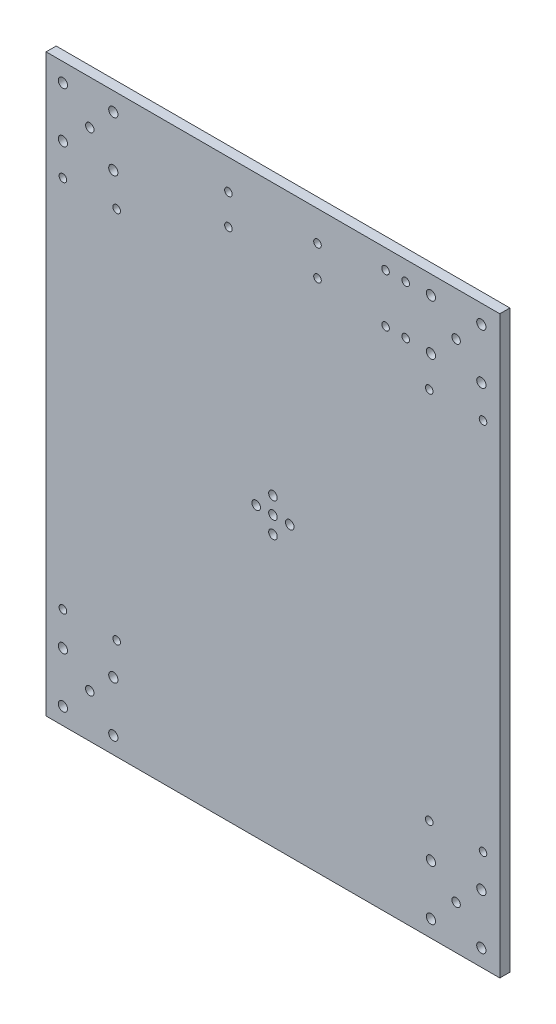
SolidWorks part; units mm, degrees
ref_plane "Спереди" through (0, 0, 0) normal (0, 0, 1) x (1, 0, 0)
ref_plane "Сверху" through (0, 0, 0) normal (0, 1, 0) x (1, 0, 0)
ref_plane "Справа" through (0, 0, 0) normal (1, 0, 0) x (0, 0, -1)
sketch "Эскиз3" plane through (0, 0, 0) normal (0, 0, 1) x (1, 0, 0)
  line L0 (0, 0) -> (0, 10) construction
  line L5 (135, -171.15) -> (-135, -171.15)
  line L6 (135, -171.15) -> (135, 171.15)
  line L7 (135, 171.15) -> (-135, 171.15)
  line L8 (-135, -171.15) -> (-135, 171.15)
  line L9 (0, 0) -> (10, 0) construction
  line L10 (0, 0) -> (0, -10) construction
  line L11 (0, 0) -> (-10, 0) construction
  line L12 (79, 130.65) -> (79, 159.65) construction
  line L13 (79, 159.65) -> (67, 159.65) construction
  line L14 (67, 159.65) -> (67, 130.65) construction
  line L15 (67, 130.65) -> (79, 130.65) construction
  circle A0 centre (0, 0) radius 2.55
  circle A1 centre (0, 10) radius 2.55
  circle A2 centre (10, 0) radius 2.55
  circle A3 centre (0, -10) radius 2.55
  circle A4 centre (-10, 0) radius 2.55
  circle A17 centre (67, 159.65) radius 2.25
  circle A18 centre (79, 159.65) radius 2.25
  circle A19 centre (67, 130.65) radius 2.25
  circle A20 centre (79, 130.65) radius 2.25
  point P0 (0, 0)
  point P5 (-135, 0)
  point P6 (0, 171.15)
  point P21 (0, 0)
  dimension "D3" = 5.1
  dimension "D4" = 5.1
  dimension "D7" = 4.5
  dimension "D1" = 342.3
  dimension "D2" = 270
  dimension "D5" = 10
  dimension "D6" = 4
extrude "Бобышка-Вытянуть1" add sketch "Эскиз3" along normal blind 6
sketch "Эскиз4" plane through (0, 0, 6) normal (0, 0, 1) x (1, 0, 0)
  line L0 (135, 171.15) -> (-135, 171.15) construction
  line L1 (-135, 171.15) -> (-135, -171.15) construction
  circle A0 centre (-109, 145.15) radius 2.5
  dimension "D1" = 5
  dimension "D2" = 26
  dimension "D3" = 26
extrude "Вырез-Вытянуть1" cut sketch "Эскиз4" against normal through all contours A0
pattern_linear "Линейный массив1" count 2 spacing 218 along (1, 0, 0) count 2 spacing 290.3 along (0, -1, 0) of "Вырез-Вытянуть1"
sketch "Эскиз7" plane through (0, 0, 0) normal (0, 0, -1) x (-1, 0, 0)
  line L9 (-26.5, 153.15) -> (26.5, 153.15) construction
  line L10 (-26.5, 153.15) -> (-26.5, 135.15) construction
  line L11 (-26.5, 135.15) -> (26.5, 135.15) construction
  line L16 (26.5, 153.15) -> (26.5, 135.15) construction
  line L17 (-135, 171.15) -> (135, 171.15) construction
  circle A0 centre (-26.5, 153.15) radius 2.25
  circle A1 centre (26.5, 153.15) radius 2.25
  circle A2 centre (-26.5, 135.15) radius 2.25
  circle A3 centre (26.5, 135.15) radius 2.25
  point P4 (0, 135.15)
  dimension "D4" = 4.5
  dimension "D5" = 4.5
  dimension "D6" = 4.5
  dimension "D7" = 4.5
  dimension "D1" = 53
  dimension "D2" = 18
  dimension "D3" = 18
extrude "Вырез-Вытянуть2" cut sketch "Эскиз7" against normal through all
sketch "Эскиз8" plane through (0, 0, 0) normal (0, 0, -1) x (-1, 0, 0)
  line L0 (93, 111.15) -> (125, 111.15) construction
  line L8 (135, 171.15) -> (135, -171.15) construction
  line L9 (-135, 171.15) -> (135, 171.15) construction
  circle A4 centre (93, 111.15) radius 2.25
  circle A5 centre (125, 111.15) radius 2.25
  dimension "D3" = 32
  dimension "D4" = 10
  dimension "D5" = 60
  dimension "D1" = 4.5
  dimension "D2" = 4.5
extrude "Вырез-Вытянуть3" cut sketch "Эскиз8" against normal through all
pattern_linear "Линейный массив2" count 2 spacing 222.3 along (0, -1, 0) count 2 spacing 218 along (1, 0, 0) of "Вырез-Вытянуть3"
sketch "Эскиз10" plane through (0, 0, 0) normal (0, 0, -1) x (-1, 0, 0)
  line L0 (-124, 130.15) -> (-94, 130.15) construction
  line L1 (-129, 125.15) -> (-89, 125.15) construction
  line L2 (-129, 125.15) -> (-129, 165.15) construction
  line L3 (-129, 165.15) -> (-89, 165.15) construction
  line L4 (-89, 125.15) -> (-89, 165.15) construction
  line L5 (-129, 125.15) -> (-89, 165.15) construction
  line L6 (-129, 165.15) -> (-89, 125.15) construction
  line L8 (-94, 130.15) -> (-94, 160.15) construction
  line L10 (-94, 160.15) -> (-124, 160.15) construction
  circle A0 centre (-124, 160.15) radius 2.75
  circle A1 centre (-94, 160.15) radius 2.75
  circle A2 centre (-94, 130.15) radius 2.75
  circle A3 centre (-124, 130.15) radius 2.75
  point P0 (-109, 145.15)
  dimension "D2" = 5.5
  dimension "D1" = 40
  dimension "D3" = 30
extrude "Вырез-Вытянуть4" cut sketch "Эскиз10" against normal through all
pattern_linear "Линейный массив3" count 2 spacing 219 along (-1, 0, 0) count 2 spacing 291.3 along (0, -1, 0) of "Вырез-Вытянуть4"
equation "\"Ширина груза\"= 160"
equation "\"Глубина груза\"= 240"
equation "\"Высота груза\"= 160"
equation "\"Ширина ячейки\"= \"Ширина груза\" + 10"
equation "\"Глубина ячейки\"= \"Глубина груза\" + 10"
equation "\"Высота ячейки\"= \"Высота груза\" + 10 + 13"
equation "\"Колво ячеек ширина\"= 2"
equation "\"Колво ячеек высота\"= 2"
equation "\"Толщина стенки\" = \"Толщина тонких панелей\""
equation "\"Крепление дверцы\"= 5 "
equation "\"Ширина рейки\"= \"Толщина шестерни\""
equation "\"Высота рейки\"= 20"
equation "\"Высота пола\" = 2*\"Толщина тонких панелей\""
equation "\"Колво полозьев\"= 5"
equation "\"Отступ рейки\"= 20"
equation "\"Глубина каретки\"= \"Глубина ячейки\" + 30 + \"Мотор Y высота корпуса\" + 20"
equation "\"Длинна рейки\" = (\"Ширина ячейки\"+\"Толщина вертикальных стенок\"+\"Крепление дверцы\")*\"Колво ячеек ширина\"+\"Ширина ячейки выгрузки\"*\"Колво выгрузки\"+\"Толщина вертикальных стенок\"+2*\"Отступ крепления мотора фиксации\"-\"Крепление дверцы\"*\"Колво ячеек ширина\""
equation "\"Отступ шпильки\"= 26"
equation "\"Диаметр шпильки\"= 5"
equation "\"D1@Бобышка-Вытянуть1\" = \"Толщина стенки\""
equation "\"D1@Эскиз4\"= \"Диаметр шпильки\""
equation "\"D2@Эскиз4\"=\"Отступ шпильки\""
equation "\"D3@Эскиз4\"= \"Отступ шпильки\""
equation "\"D2@Эскиз3\"=\"Ширина ячейки\" + \"Ширина пластины\" * 2"
equation "\"D1@Эскиз3\"=\"Глубина каретки\" "
equation "\"D3@Линейный массив1\"=\"Ширина ячейки\"  +\"Ширина пластины\" *2 - \"Отступ шпильки\" * 2"
equation "\"D4@Линейный массив1\"=\"Глубина каретки\" + \"Ширина рейки\" * 2 - \"Отступ шпильки\" * 2 - \"Ширина рейки\" * 2"
equation "\"Длинна шпильки\" = (\"Высота ячейки\"+\"Толщина горизонтальных плит\"+\"Высота пола\")*\"Колво ячеек высота\"+2*(\"Толщина горизонтальных плит\"+\"Отступ рейки\")"
equation "\"Ширина пластины\"= 50  "
equation "\"Высота зона выгрузки\"= \"Высота ячейки\" * 2 + \"Толщина стенки\" * 2"
equation "\"Колво выгрузки\"= 1"
equation "\"Отступ крепления мотора фиксации\" = (\"Ширина пластины\"+20-\"Толщина вертикальных стенок\")/2"
equation "\"Мотор X ширина корпуса\"= 42.3"
equation "\"Мотор X высота корпуса\"= 42.3"
equation "\"Мотор X длина корпуса\"= 40"
equation "\"Мотор X вылет вала\"= 19.8"
equation "\"Мотор Y ширина корпуса\"= 42.3"
equation "\"Мотор Y высота корпуса\"= 42.3"
equation "\"Мотор Y длина корпуса\"= 48"
equation "\"Мотор Y вылет вала\"= 30"
equation "\"Мотор Z ширина корпуса\"= 42"
equation "\"Мотор Z высота корпуса\"= 42"
equation "\"Мотор Z длина корпуса\"= 40"
equation "\"Мотор Z вылет вала\"= 23"
equation "\"Мотор диаметр вала ПРЕДВ\"= 5"
equation "\"Мотор шаг крепления ПРЕДВ\"= 31"
equation "\"Мотор диаметр отверстий ПРЕДВ\"= 3"
equation "\"Мотор глубина отверстий ПРЕДВ\"= 4.5"
equation "\"Мотор диаметр буртика ПРЕДВ\"= 22"
equation "\"Мотор высота буртика ПРЕДВ\"= 2"
equation "\"Мотор диаметр шкива ПРЕДВ\"= 16"
equation "\"Мотор длина шкива ПРЕДВ\"= 12"
equation "\"Мотор отступ шкива ПРЕДВ\"= 5"
equation "\"Мотор X шаг градусов\"= 1.8"
equation "\"Мотор Y шаг градусов\"= 1.8"
equation "\"Мотор Z шаг градусов\"= 1.8"
equation "\"Мотор Y диаметр ротора\"= 25.78"
equation "\"Толщина шестерни\"= 10"
equation "\"Ширина ячейки выгрузки\" = \"Ширина ячейки\"+\"Толщина вертикальных стенок\"+2*\"Отступ крепления мотора фиксации\""
equation "\"D3@Линейный массив2\" = \"Глубина каретки\"-120"
equation "\"D4@Линейный массив2\" = \"Ширина ячейки\"+2*\"Ширина пластины\"-2*\"Отступ шпильки\""
equation "\"Толщина тонких панелей\" = 6"
equation "\"Толщина вертикальных стенок\" = 6"
equation "\"Толщина горизонтальных плит\" = 6"
equation "\"Базовая высота корпуса\"= (\"Высота ячейки\"+\"Толщина тонких панелей\"+\"Высота пола\")*\"Колво ячеек высота\"+6*\"Толщина тонких панелей\"+\"Мотор X ширина корпуса\"+\"Мотор Y ширина корпуса\"+75"
equation "\"Высота корпуса\"= (\"Высота ячейки\"+\"Толщина горизонтальных плит\"+\"Высота пола\")*\"Колво ячеек высота\"+2*\"Толщина горизонтальных плит\"+4*\"Толщина тонких панелей\"+\"Мотор X ширина корпуса\"+\"Мотор Y ширина корпуса\"+75"
equation "\"Смещение центра корпуса\"= (\"Высота корпуса\"-\"Базовая высота корпуса\")/2-(\"Толщина горизонтальных плит\"-\"Толщина тонких панелей\")"
equation "\"Отметка пола\"= -\"Базовая высота корпуса\"/2+\"Толщина тонких панелей\""
equation "\"Отметка потолка\"= \"Отметка пола\"+\"Высота корпуса\"-2*\"Толщина горизонтальных плит\""
equation "\"Отметка верхней полки\"= \"Отметка потолка\"-(28+\"Толщина тонких панелей\")-\"Высота ячейки\"-\"Высота пола\""
equation "\"Отметка нижней полки\"= \"Отметка верхней полки\"-\"Высота ячейки\"-\"Высота пола\"-\"Толщина горизонтальных плит\""
